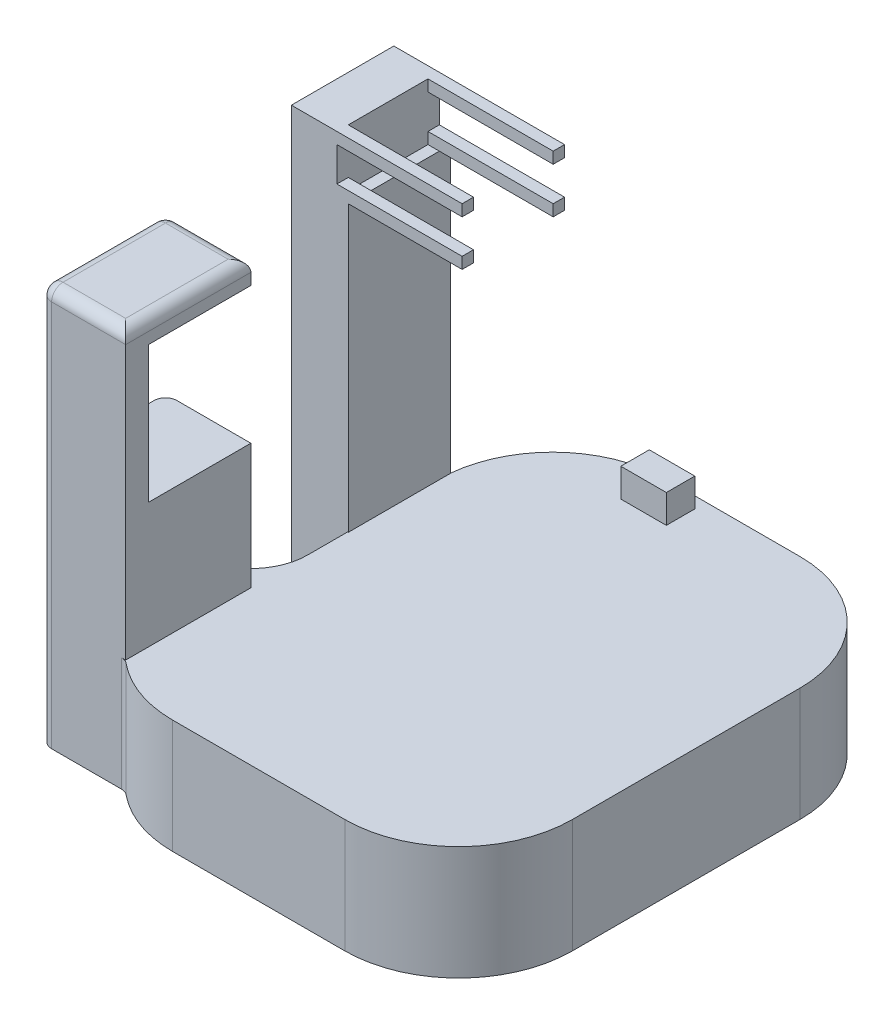
SolidWorks part; units mm, degrees
ref_plane "Front Plane" through (0, 0, 0) normal (0, 0, 1) x (1, 0, 0)
ref_plane "Top Plane" through (0, 0, 0) normal (0, 1, 0) x (1, 0, 0)
ref_plane "Right Plane" through (0, 0, 0) normal (1, 0, 0) x (0, 0, -1)
sketch "Sketch5" plane through (0, 0, 0) normal (0, 1, 0) x (1, 0, 0)
  line L1 (31.75, 40) -> (-31.75, 40)
  line L2 (31.75, 40) -> (31.75, -40)
  line L3 (31.75, -40) -> (-31.75, -40)
  line L4 (-31.75, 40) -> (-31.75, -40)
  line L5 (31.75, 40) -> (-31.75, -40) construction
  line L6 (31.75, -40) -> (-31.75, 40) construction
  point P0 (0, 0)
  dimension "D1" = 80
  dimension "D2" = 63.5
extrude "Boss-Extrude4" add sketch "Sketch5" along normal blind 20
sketch "Sketch6" plane through (0, 20, 0) normal (0, 1, 0) x (1, 0, 0)
  line L0 (31.75, 40) -> (-31.75, 40) construction
  line L1 (-4.75, 38) -> (-12.75, 38)
  line L2 (-4.75, 38) -> (-4.75, 33)
  line L3 (-4.75, 33) -> (-12.75, 33)
  line L4 (-12.75, 38) -> (-12.75, 33)
  line L5 (-4.75, 38) -> (-12.75, 33) construction
  line L6 (-4.75, 33) -> (-12.75, 38) construction
  line L9 (0, 0) -> (0, 40) construction
  line L10 (-31.75, 40) -> (-31.75, -40) construction
  point P0 (-8.75, 35.5)
  dimension "D1" = 8
  dimension "D2" = 5
  dimension "D3" = 2
  dimension "D4" = 19
extrude "Boss-Extrude5" add sketch "Sketch6" along normal blind 5 contours L3 L4 L1 L2
sketch "Sketch9" plane through (0, 0, 0) normal (0, 1, 0) x (1, 0, 0)
  line L0 (-31.75, 40) -> (-31.75, -40) construction
  line L5 (-31.75, -35) -> (-46.75, -35)
  line L6 (-31.75, -35) -> (-31.75, -13)
  line L7 (-31.75, -13) -> (-46.75, -13)
  line L8 (-46.75, -35) -> (-46.75, -13)
  line L9 (-31.75, -40) -> (31.75, -40) construction
  point P13 (-39.25, -13)
  dimension "D4" = 5
  dimension "D5" = 22
  dimension "D6" = 7.5
sketch "Sketch13" plane through (0, 20, 0) normal (0, 1, 0) x (1, 0, 0)
  line L0 (-31.75, 40) -> (-31.75, -40) construction
  line L2 (-31.75, -40) -> (31.75, -40) construction
  circle A0 centre (-27.6098, -10) radius 3
  circle A1 centre (23.8252, -10) radius 3
  circle A2 centre (-1.905, -25.24) radius 3
  dimension "D1" = 4.1402
  dimension "D3" = 6
  dimension "D4" = 51.435
  dimension "D6" = 6
  dimension "D7" = 6
  dimension "D2" = 30
  dimension "D5" = 25.7302
  dimension "D8" = 25.7048
  dimension "D9" = 15.24
extrude "Boss-Extrude8" [suppressed] add sketch "Sketch13" along normal blind 20
extrude "Boss-Extrude10" add sketch "Sketch9" along normal blind 70 contours L8 L7 L6 L5
sketch "Sketch14" plane through (0, 0, 13) normal (0, 0, -1) x (-1, 0, 0)
  line L0 (31.75, 70) -> (31.75, 20) construction
  line L1 (31.75, 42) -> (46.75, 42)
  line L2 (31.75, 42) -> (31.75, 66)
  line L3 (31.75, 66) -> (46.75, 66)
  line L4 (46.75, 42) -> (46.75, 66)
  line L5 (46.75, 70) -> (46.75, 0) construction
  line L7 (31.75, 0) -> (46.75, 0) construction
  dimension "D1" = 42
  dimension "D2" = 24
extrude "Cut-Extrude1" cut sketch "Sketch14" against normal blind 18 contours L3 L4 L1 L2
fillet "Fillet1" radius 20 4 edges at (-31.75, 10, -40) (31.75, 10, -40) (-31.75, 10, 40) (31.75, 10, 40)
fillet "Fillet2" radius 10 1 edges at (-31.75, 10, 13)
fillet "Fillet3" radius 2 3 edges at (-31.75, 10, 35) (-46.75, 35, 35) (-46.75, 21, 13)
fillet "Fillet4" radius 2 1 edges at (-46.75, 68, 13)
fillet "Fillet6" radius 2 6 edges at (-31.75, 70, 24) (-38.25, 70, 35) (-46.1642, 70, 34.4142) (-46.75, 70, 24) (-46.1642, 70, 13.5858) (-38.25, 70, 13)
sketch "Sketch15" [suppressed] plane through (0, 40, 0) normal (0, 1, 0) x (1, 0, 0)
  circle A0 centre (23.8252, -10) radius 1.6383
  circle A1 centre (23.8252, -10) radius 3 construction
  circle A2 centre (-1.905, -25.24) radius 2
  circle A3 centre (-1.905, -25.24) radius 3 construction
  circle A5 centre (-27.6098, -10) radius 2.5
  dimension "D1" = 3.2766
  dimension "D3" = 4
  dimension "D4" = 5
  dimension "D2" = 0
  dimension "D5" = 0
extrude "Cut-Extrude2" [suppressed] cut sketch "Sketch15" against normal blind 1 draft 8
sketch "Sketch16" [suppressed] plane through (0, 39, 0) normal (0, 1, 0) x (1, 0, 0)
  circle A0 centre (23.8252, -10) radius 1.4986
  circle A1 centre (23.8252, -10) radius 3 construction
  circle A2 centre (-1.905, -25.24) radius 2
  circle A3 centre (-27.6098, -10) radius 2.5
  circle A5 centre (-1.905, -25.24) radius 3 construction
  dimension "D1" = 2.9972
  dimension "D3" = 4
  dimension "D4" = 5
  dimension "D2" = 0
  dimension "D6" = 0
extrude "Cut-Extrude3" [suppressed] cut sketch "Sketch16" against normal blind 7
sketch "Sketch18" plane through (0, 0, 0) normal (0, -1, 0) x (-1, 0, 0)
  line L0 (41.75, -13) -> (44.75, -13) construction
  line L1 (31.6319, 22) -> (41.6319, 22)
  line L2 (31.6319, 22) -> (31.6319, 4)
  line L3 (31.6319, 4) -> (41.6319, 4)
  line L4 (41.6319, 22) -> (41.6319, 4)
  point P4 (32.6009, 13.424)
  dimension "D1" = 17
  dimension "D2" = 41.6319
  dimension "D3" = 18
  dimension "D4" = 10
extrude "Boss-Extrude11" add sketch "Sketch18" against normal blind 80 contours L1 L4 L3 L2
sketch "Sketch19" plane through (0, 80, 0) normal (0, 1, 0) x (1, 0, 0)
  line L1 (-31.6319, 22) -> (-11.6319, 22)
  line L2 (-31.6319, 22) -> (-31.6319, 14.7413)
  line L3 (-31.6319, 6.7413) -> (-31.6319, 14.7413)
  line L4 (-11.6319, 22) -> (-11.6319, 14.7413)
  line L5 (-31.6319, 4) -> (-11.6319, 4)
  line L6 (-31.6319, 4) -> (-31.6319, 6.7413)
  line L8 (-11.6319, 4) -> (-11.6319, 6.7413)
  line L9 (-11.6319, 6.7413) -> (-11.6319, 14.7413)
  point P9 (-50.6726, -14.8204)
  dimension "D3" = 20
extrude "Boss-Extrude12" add sketch "Sketch19" against normal blind 10
sketch "Sketch20" plane through (-11.6319, 0, 0) normal (1, 0, 0) x (0, 0, -1)
  line L0 (4, 80) -> (22, 80) construction
  line L1 (20, 80) -> (6, 80)
  line L2 (20, 80) -> (20, 78)
  line L3 (20, 70) -> (6, 70)
  line L4 (6, 80) -> (6, 78)
  line L5 (4, 70) -> (22, 70) construction
  line L7 (4, 72) -> (6, 72)
  line L8 (4, 72) -> (4, 78)
  line L9 (4, 78) -> (6, 78)
  line L10 (22, 72) -> (22, 78)
  line L11 (22, 70) -> (22, 80) construction
  line L12 (4, 70) -> (4, 80) construction
  line L13 (6, 72) -> (6, 70)
  line L14 (20, 78) -> (22, 78)
  line L15 (20, 72) -> (20, 70)
  line L16 (20, 72) -> (22, 72)
  point P8 (13, 80)
  dimension "D1" = 7
  dimension "D2" = 2
  dimension "D3" = 2
  dimension "D4" = 0
  dimension "D5" = 2
extrude "Cut-Extrude4" cut sketch "Sketch20" against normal blind 22 contours L9 L4 L1 L2 L14 L10 L16 L15 L3 L13 L7 L8
